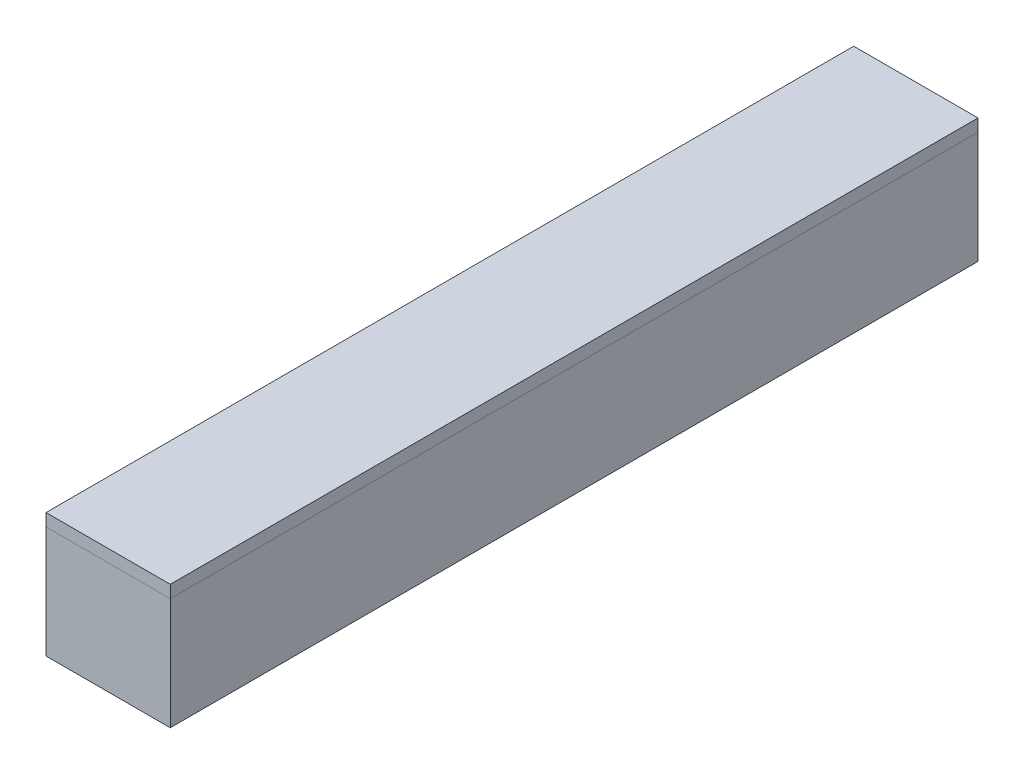
SolidWorks part; units mm, degrees
ref_plane "Front Plane" through (0, 0, 0) normal (0, 0, 1) x (1, 0, 0)
ref_plane "Top Plane" through (0, 0, 0) normal (0, 1, 0) x (1, 0, 0)
ref_plane "Right Plane" through (0, 0, 0) normal (1, 0, 0) x (0, 0, -1)
sketch "Sketch1" plane through (0, 0, 0) normal (0, 1, 0) x (1, 0, 0)
  line L0 (-1004.5712, -32.5) -> (48995.4288, -32.5) construction
  line L1 (0, 0) -> (-10, 0)
  line L2 (0, 0) -> (0, -65)
  line L3 (0, -65) -> (-10, -65)
  line L4 (-10, 0) -> (-10, -65)
  line L5 (-8.2244, -27.9935) -> (-7.797, -21.0065)
  line L6 (-8.2244, -27.9935) -> (-1.2244, -27.9935)
  line L7 (-7.797, -21.0065) -> (-0.797, -21.0065)
  line L8 (-1.2244, -27.9935) -> (-0.797, -21.0065)
  line L9 (-7.797, -21.0065) -> (-1.2244, -27.9935) construction
  line L10 (-8.2244, -27.9935) -> (-0.797, -21.0065) construction
  line L11 (-9.8865, -112.393) -> (-4.8019, -29.2606) construction
  line L12 (-5, 0) -> (-5, -65) construction
  line L13 (-8.7756, -37.0065) -> (-2.203, -43.9935) construction
  line L14 (-1.7756, -37.0065) -> (-9.203, -43.9935) construction
  line L15 (-8.7756, -37.0065) -> (-1.7756, -37.0065)
  line L16 (-8.7756, -37.0065) -> (-9.203, -43.9935)
  line L17 (-1.7756, -37.0065) -> (-2.203, -43.9935)
  line L18 (-9.203, -43.9935) -> (-2.203, -43.9935)
  point P7 (-10, -32.5)
  point P9 (-5, -32.5)
  point P18 (-5.4893, -40.5)
  point P19 (-4.5107, -24.5)
  point P25 (-4.5107, -24.5)
  point P26 (-5.4893, -40.5)
  point P27 (0, 0)
  point P28 (-8.2244, -45.6149)
  point P29 (0, 0)
  dimension "D1" = 7
  dimension "D2" = 8
  dimension "D3" = 7
  dimension "D4" = 8
extrude "Boss-Extrude1" add sketch "Sketch1" against normal blind 0.64 contours L6 L8 L7 L5 | L16 L18 L17 L15 | L1 L4 L3 L2 L18 L16 L15 L17 L8 L6 L5 L7 region at (-5, 0, 32.5) region at (-4.5107, 0, 24.5) region at (-5.4893, 0, 40.5)
extrude "Boss-Extrude2" add sketch "Sketch1<2>" against normal blind 10
sketch "Sketch1<2>" plane through (0, 0, 0) normal (0, 1, 0) x (1, 0, 0) same geometry as "Sketch1"
ref_plane "Plane1" through (0, -1, 0) normal (0, 1, 0) x (1, 0, 0)
split "Split1" trim tools "Plane1" bodies to split 102 resulting bodies 103 104
